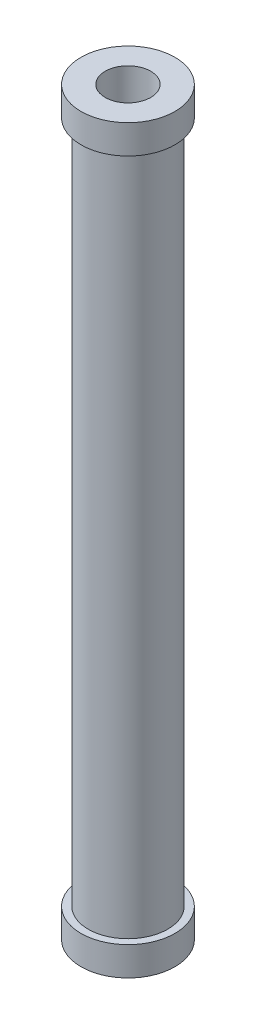
SolidWorks part; units mm, degrees
ref_plane "Front Plane" through (0, 0, 0) normal (0, 0, 1) x (1, 0, 0)
ref_plane "Top Plane" through (0, 0, 0) normal (0, 1, 0) x (1, 0, 0)
ref_plane "Right Plane" through (0, 0, 0) normal (1, 0, 0) x (0, 0, -1)
sketch "Sketch1" plane through (0, 0, 0) normal (0, 1, 0) x (1, 0, 0)
  circle A0 centre (0, 0) radius 1.575
  circle A1 centre (0, 0) radius 2.75
  circle A2 centre (0, 0) radius 3.25
  dimension "D1" = 3.15
  dimension "D2" = 5.5
  dimension "D3" = 6.5
extrude "Boss-Extrude1" add sketch "Sketch1" along normal blind 51.25 contours A1 A0 region at (-2.6722, 0, 0)
extrude "Boss-Extrude2" add sketch "Sketch1<3>" along normal blind 2 contours A2 A1 region at (-3.1581, 0, 0)
sketch "Sketch1<3>" plane through (0, 0, 0) normal (0, 1, 0) x (1, 0, 0) same geometry as "Sketch1"
extrude "Boss-Extrude3" add sketch "Sketch1<4>" along normal blind 2 from offset 49.25 contours A2 A1 region at (-3.1581, 0, 0)
sketch "Sketch1<4>" plane through (0, 0, 0) normal (0, 1, 0) x (1, 0, 0) same geometry as "Sketch1"
